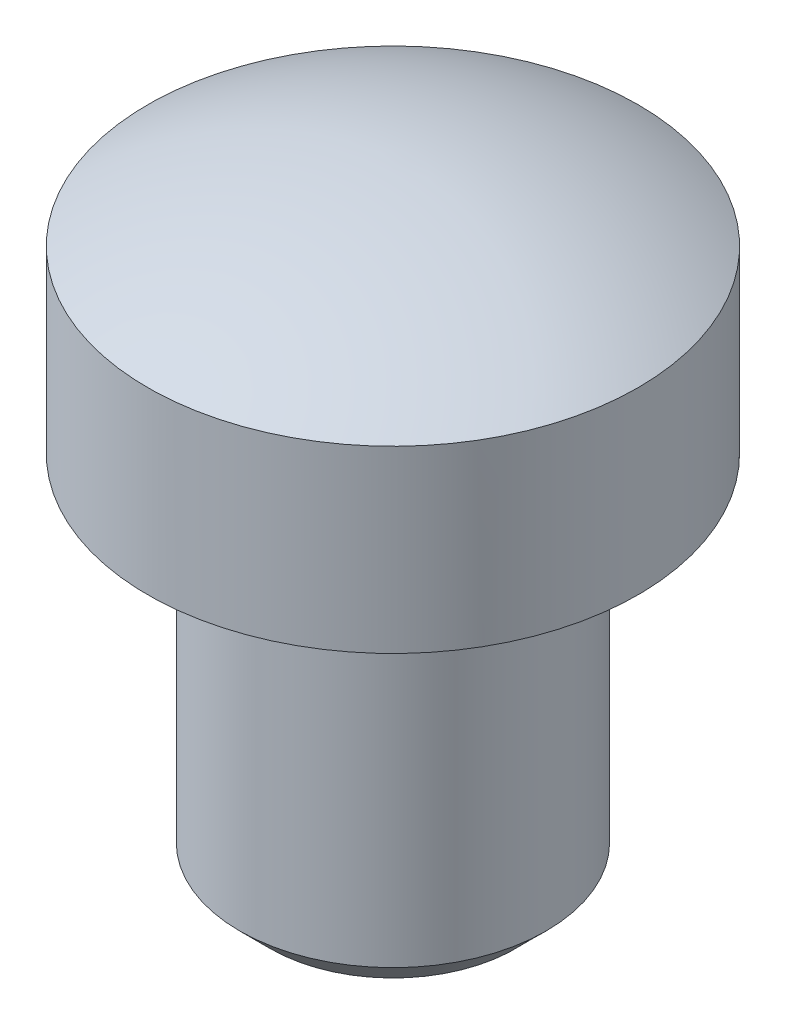
SolidWorks part; units mm, degrees
material "AISI 304"
ref_plane "前视基准面" through (0, 0, 0) normal (0, 0, 1) x (1, 0, 0)
ref_plane "上视基准面" through (0, 0, 0) normal (0, 1, 0) x (1, 0, 0)
ref_plane "右视基准面" through (0, 0, 0) normal (1, 0, 0) x (0, 0, -1)
sketch "草图1" plane through (0, 0, 0) normal (0, 0, 1) x (1, 0, 0)
  line L1 (8, -2.1436) -> (8, -8)
  line L2 (8, -8) -> (4, -8)
  line L3 (4, -8) -> (4, -9)
  line L4 (4, -9) -> (5, -9)
  line L5 (5, -9) -> (5, -20)
  line L6 (5, -20) -> (0, -20)
  line L7 (0, -20) -> (0, 0)
  arc A0 (8, -2.1436) -> (0, 0) centre (0, -16) ccw
  dimension "D1" = 16
  dimension "D2" = 8
  dimension "D3" = 20
  dimension "D4" = 5
  dimension "D5" = 1
  dimension "D6" = 1
revolve "旋转1" add sketch "草图1" angle 360 about L7
chamfer "倒角1" distance 1 angle 45 2 edges at (0, -20, -5) (0, -9, -5)
